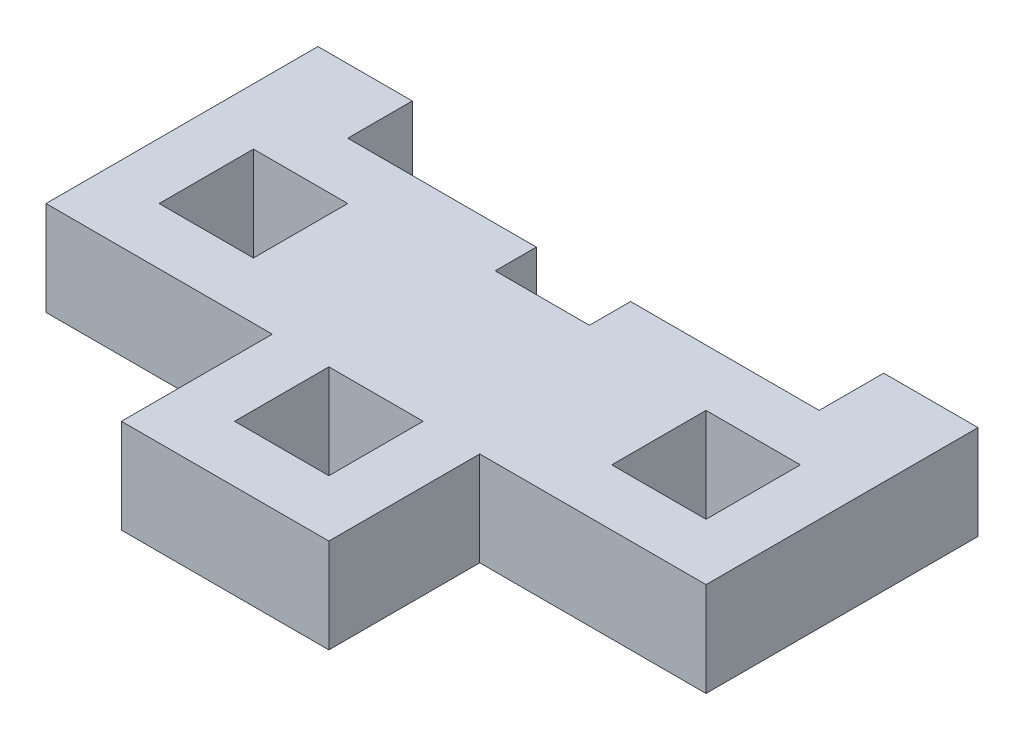
SolidWorks part; units mm, degrees
ref_plane "Front Plane" through (0, 0, 0) normal (0, 0, 1) x (1, 0, 0)
ref_plane "Top Plane" through (0, 0, 0) normal (0, 1, 0) x (1, 0, 0)
ref_plane "Right Plane" through (0, 0, 0) normal (1, 0, 0) x (0, 0, -1)
sketch "Sketch1" plane through (0, 0, 0) normal (0, 1, 0) x (1, 0, 0)
  line L0 (-22.225, 0) -> (22.225, 0) construction
  line L1 (-22.225, -6.985) -> (-6.985, -6.985)
  line L2 (-22.225, -6.985) -> (-22.225, 6.985)
  line L3 (-15.875, 6.985) -> (-3.175, 6.985)
  line L4 (22.225, -6.985) -> (22.225, 6.985)
  line L5 (0, 4.2125) -> (0, -5.6522) construction
  line L6 (-3.175, 6.985) -> (-3.175, 4.2125)
  line L7 (-3.175, 4.2125) -> (3.175, 4.2125)
  line L8 (3.175, 4.2125) -> (3.175, 6.985)
  line L9 (3.175, 6.985) -> (15.875, 6.985)
  line L10 (-6.985, -6.985) -> (-6.985, -17.145)
  line L11 (-6.985, -17.145) -> (6.985, -17.145)
  line L12 (6.985, -17.145) -> (6.985, -6.985)
  line L13 (0, -5.6522) -> (0, -17.145) construction
  line L14 (6.985, -6.985) -> (22.225, -6.985)
  line L15 (22.225, 6.985) -> (22.225, 11.33)
  line L16 (-3.175, -6.985) -> (3.175, -6.985)
  line L17 (-3.175, -6.985) -> (-3.175, -13.335)
  line L18 (-3.175, -13.335) -> (3.175, -13.335)
  line L19 (3.175, -6.985) -> (3.175, -13.335)
  line L20 (-3.175, -6.985) -> (3.175, -13.335) construction
  line L21 (-3.175, -13.335) -> (3.175, -6.985) construction
  line L22 (18.415, -3.175) -> (12.065, -3.175)
  line L23 (18.415, -3.175) -> (18.415, 3.175)
  line L24 (18.415, 3.175) -> (12.065, 3.175)
  line L25 (12.065, -3.175) -> (12.065, 3.175)
  line L26 (22.225, 11.33) -> (15.875, 11.33)
  line L27 (15.875, 11.33) -> (15.875, 6.985)
  line L28 (-15.875, 11.33) -> (-15.875, 6.985)
  line L29 (-22.225, 11.33) -> (-15.875, 11.33)
  line L30 (-12.065, -3.175) -> (-12.065, 3.175)
  line L31 (-18.415, 3.175) -> (-12.065, 3.175)
  line L32 (-18.415, -3.175) -> (-18.415, 3.175)
  line L33 (-18.415, -3.175) -> (-12.065, -3.175)
  line L34 (-22.225, 6.985) -> (-22.225, 11.33)
  point P8 (0, 0)
  point P12 (0, 4.2125)
  point P19 (0, -17.145)
  point P20 (0, -10.16)
  dimension "D1" = 44.45
  dimension "D2" = 3.81
  dimension "D3" = 6.35
  dimension "D4" = 6.35
  dimension "D5" = 3.81
  dimension "D6" = 6.35
  dimension "D7" = 3.81
  dimension "D8" = 3.81
  dimension "D9" = 2.7725
  dimension "D10" = 4.345
  dimension "D11" = 6.35
  dimension "D12" = 3.81
extrude "Boss-Extrude1" add sketch "Sketch1" along normal blind 6.35
equation "\"Ball Diameter\"= 1.75in"
equation "\"Sheet Thickness\"= 0.25in"
equation "\"Screw Diameter\"= .17in"
equation "\"Robot Diameter\"= 14in"
equation "\"Castor Screw Diameter\"= 0.22in"
equation "\"Wheel Diameter\" = 4in"
equation "\"Nut Diameter\" = 8.4mm"
equation "\"Nut Height\" = 2.9mm"
equation "\"Screw Height\" = 0.55in"
equation "\"Pulley Diameter\" = 1in"
equation "\"Reactor Height\" = 14in"
equation "\"Elevator Height\" = 11.5in"
equation "\"Elevator Width\" = \"Ball Diameter\" + 0.25in"
equation "\"Elevator Bearing Diameter\" = sqr(2*(\"Sheet Thickness\"^2)) + 0.2in"
equation "\"Elevator Axle Endcap Diameter\" = \"Pulley Diameter\" + 0.25in"
equation "\"Elevator Axle Length\" = \"Elevator Width\" + 8*\"Sheet Thickness\""
equation "\"Elevator Clearance from Axis\" = (\"Pulley Diameter\"/2) + \"Ball Diameter\" + 0.5in"
equation "\"D1@Sketch1\"=\"Elevator Width\"-0.25in"
equation "\"D3@Sketch1\" = \"Sheet Thickness\""
equation "\"D4@Sketch1\"=\"Sheet Thickness\""
equation "\"D6@Sketch1\"=\"Sheet Thickness\""
equation "\"D9@Sketch1\"=(0.3in - ((\"Elevator Axle Endcap Diameter\"-\"Pulley Diameter\")/2 - 1.1mm))/2"
equation "\"D10@Sketch1\"=(\"Elevator Axle Endcap Diameter\"-\"Pulley Diameter\")/2 - 1.1mm + 2.27mm"
equation "\"D1@Boss-Extrude1\"=\"Sheet Thickness\""
